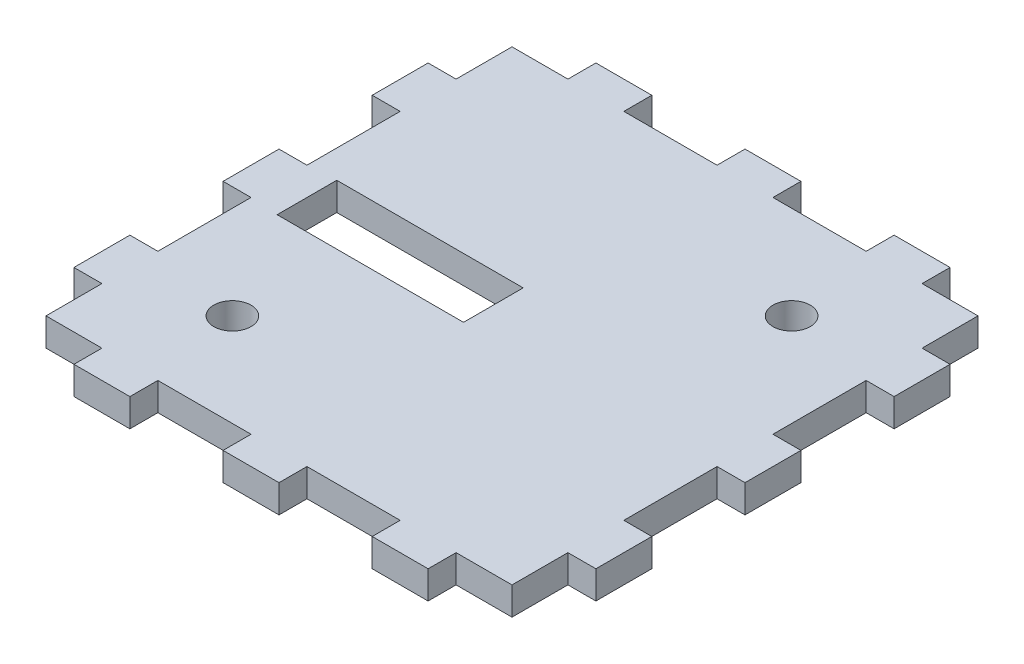
SolidWorks part; units mm, degrees
material "Acrylic (Medium-high impact)"
ref_plane "Front Plane" through (0, 0, 0) normal (0, 0, 1) x (1, 0, 0)
ref_plane "Top Plane" through (0, 0, 0) normal (0, 1, 0) x (1, 0, 0)
ref_plane "Right Plane" through (0, 0, 0) normal (1, 0, 0) x (0, 0, -1)
sketch "Sketch1" plane through (0, 0, 0) normal (0, 1, 0) x (1, 0, 0)
  line L0 (-53, 44) -> (-50, 44)
  line L1 (0, 0) -> (-50, 0)
  line L2 (0, 0) -> (0, 50)
  line L3 (0, 50) -> (-50, 50)
  line L4 (-50, 0) -> (-50, 50)
  line L6 (-50, 50) -> (-50, 0)
  line L8 (-53, 44) -> (-53, 38)
  line L9 (-50, 50) -> (0, 50)
  line L11 (-44, 53) -> (-38, 53)
  line L21 (-53, 28) -> (-50, 28)
  line L22 (-53, 22) -> (-50, 22)
  line L23 (-53, 6) -> (-50, 6)
  line L24 (-25, 50) -> (-25, 0) construction
  line L25 (-50, 25) -> (0, 25) construction
  line L26 (-44, 53) -> (-44, 50)
  line L27 (-28, 53) -> (-28, 50)
  line L28 (-12, 53) -> (-12, 50)
  line L29 (-6, 53) -> (-6, 50)
  line L30 (-38, 53) -> (-38, 50)
  line L31 (-22, 53) -> (-22, 50)
  line L32 (-44, 53) -> (-38, 53)
  line L33 (-28, 53) -> (-22, 53)
  line L34 (-12, 53) -> (-6, 53)
  line L35 (-53, 38) -> (-50, 38)
  line L36 (-53, 38) -> (-53, 44)
  line L37 (-53, 28) -> (-53, 22)
  line L38 (-53, 12) -> (-50, 12)
  line L39 (-53, 12) -> (-53, 6)
  line L40 (-28, 53) -> (-22, 53)
  line L41 (-12, 53) -> (-6, 53)
  line L42 (-53, 28) -> (-53, 22)
  line L43 (-53, 12) -> (-53, 6)
  line L44 (-38, 51.5) -> (-28, 51.5) construction
  line L45 (-22, 51.5) -> (-12, 51.5) construction
  line L46 (-51.5, 28) -> (-51.5, 38) construction
  line L47 (-51.5, 12) -> (-51.5, 22) construction
  line L48 (3, 6) -> (0, 6)
  line L49 (3, 12) -> (3, 6)
  line L50 (3, 12) -> (0, 12)
  line L51 (3, 22) -> (0, 22)
  line L52 (3, 28) -> (3, 22)
  line L53 (3, 28) -> (0, 28)
  line L54 (3, 38) -> (0, 38)
  line L55 (3, 44) -> (3, 38)
  line L56 (3, 44) -> (0, 44)
  line L57 (-12, -3) -> (-12, 0)
  line L58 (-22, -3) -> (-22, 0)
  line L59 (-28, -3) -> (-28, 0)
  line L60 (-38, -3) -> (-38, 0)
  line L61 (-6, -3) -> (-6, 0)
  line L62 (-12, -3) -> (-6, -3)
  line L63 (-28, -3) -> (-22, -3)
  line L64 (-44, -3) -> (-38, -3)
  line L65 (-44, -3) -> (-44, 0)
  dimension "D1" = 50
  dimension "D2" = 50
  dimension "D3" = 3
  dimension "D4" = 6
  dimension "D5" = 6
  dimension "D6" = 6
  dimension "D7" = 6
  dimension "D8" = 6
extrude "Boss-Extrude1" add sketch "Sketch1" along normal blind 3 contours L38 L39 L23 L6 | L21 L37 L22 L6 | L8 L35 L4 L0 | L30 L11 L26 L3 | L4 L1 L2 L3 L9 L6 | L33 L27 L3 L31 | L34 L28 L9 L29 | L55 L56 L2 L54 | L52 L53 L2 L51 | L49 L50 L2 L48 | L57 L62 L61 L1 | L59 L63 L58 L1 | L65 L64 L60 L1 region at (-51.5, 0, -41) region at (-25, 0, -25) region at (-51.5, 0, -25) region at (-41, 0, -51.5) region at (-51.5, 0, -9) region at (-25, 0, -51.5) region at (-9, 0, -51.5) region at (-41, 0, 1.5) region at (-25, 0, 1.5) region at (1.5, 0, -41) region at (-9, 0, 1.5) region at (1.5, 0, -25) region at (1.5, 0, -9)
sketch "Sketch2" plane through (0, 3, 0) normal (0, 1, 0) x (1, 0, 0)
  line L0 (3, 28) -> (3, 22) construction
  line L1 (-47, 28.2) -> (-27, 28.2)
  line L2 (-47, 28.2) -> (-47, 21.8)
  line L3 (-47, 21.8) -> (-27, 21.8)
  line L4 (-27, 28.2) -> (-27, 21.8)
  line L6 (-28, 0) -> (-38, 0) construction
  line L7 (-50, 12) -> (-50, 22) construction
  line L8 (0, 44) -> (0, 50) construction
  line L9 (0, 50) -> (-6, 50) construction
  line L10 (-50, 28) -> (-50, 38) construction
  circle A0 centre (-40, 10) radius 2
  circle A1 centre (-10, 40) radius 2
  point P4 (-27, 25)
  point P7 (3, 25)
  dimension "D3" = 4
  dimension "D1" = 6.4
  dimension "D2" = 20
  dimension "D4" = 10
  dimension "D5" = 10
  dimension "D6" = 10
  dimension "D7" = 10
  dimension "D8" = 3
extrude "Cut-Extrude1" cut sketch "Sketch2" against normal through all
